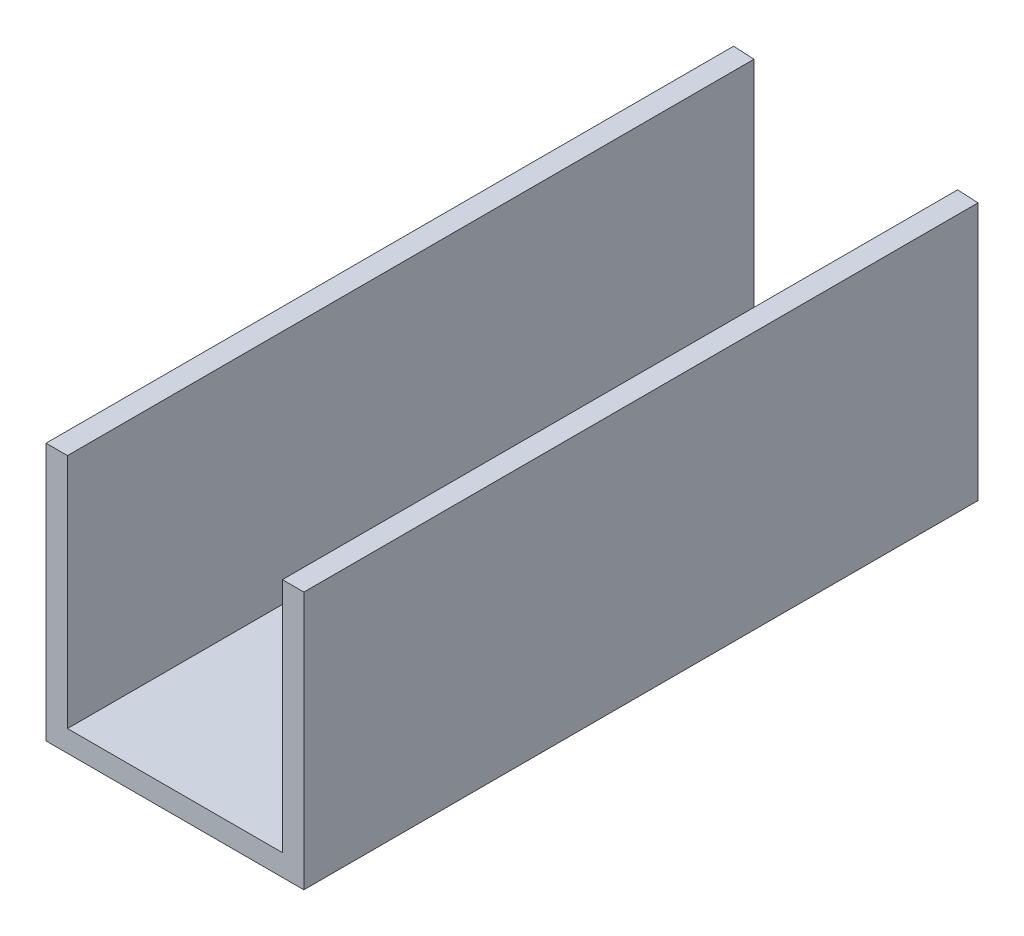
SolidWorks part; units mm, degrees
ref_plane "Front Plane" through (0, 0, 0) normal (0, 0, 1) x (1, 0, 0)
ref_plane "Top Plane" through (0, 0, 0) normal (0, 1, 0) x (1, 0, 0)
ref_plane "Right Plane" through (0, 0, 0) normal (1, 0, 0) x (0, 0, -1)
sketch "Sketch1" plane through (0, 0, 0) normal (0, 0, 1) x (1, 0, 0)
  line L0 (18.3712, 0) -> (-19.7288, 0)
  line L1 (-19.7288, 0) -> (-19.7288, 38.1)
  line L2 (-19.7288, 38.1) -> (-16.5538, 38.1)
  line L3 (-16.5538, 38.1) -> (-16.5538, 3.175)
  line L4 (-16.5538, 3.175) -> (15.1962, 3.175)
  line L5 (15.1962, 3.175) -> (15.1962, 38.1)
  line L6 (15.1962, 38.1) -> (18.3712, 38.1)
  line L7 (18.3712, 38.1) -> (18.3712, 0)
  dimension "D1" = 3.175
  dimension "D2" = 3.175
  dimension "D3" = 3.175
  dimension "D4" = 38.1
  dimension "D5" = 38.1
  dimension "D6" = 38.1
extrude "Boss-Extrude1" add sketch "Sketch1" along normal blind 101.6
sketch "Sketch2" plane through (0, 38.1, 0) normal (0, 1, 0) x (1, 0, 0)
  line L0 (-19.7288, 0) -> (18.3712, 0)
  line L1 (18.3712, 0) -> (18.3712, -1.9967)
  line L2 (18.3712, -101.6) -> (18.3712, 0) construction
  line L3 (18.3712, -1.9967) -> (-19.7288, 0)
  dimension "D1" = 3
extrude "Cut-Extrude1" cut sketch "Sketch2" against normal blind 98.425
